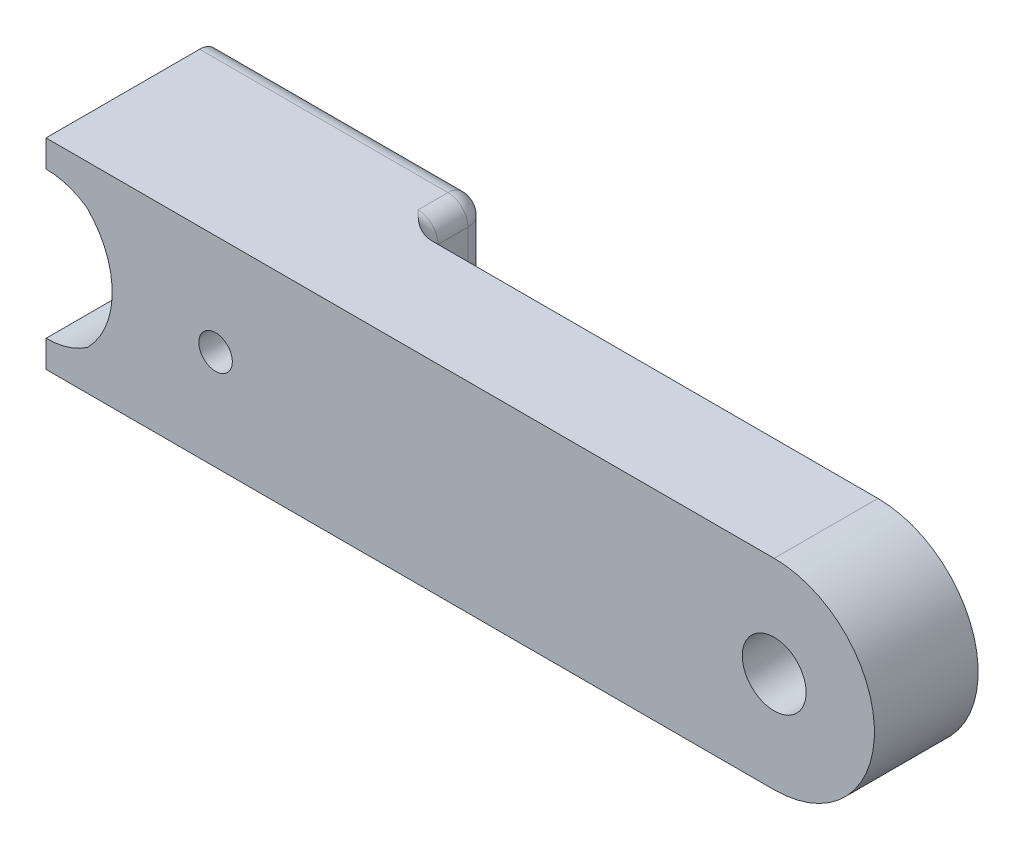
SolidWorks part; units mm, degrees
ref_plane "前视基准面" through (0, 0, 0) normal (0, 0, 1) x (1, 0, 0)
ref_plane "上视基准面" through (0, 0, 0) normal (0, 1, 0) x (1, 0, 0)
ref_plane "右视基准面" through (0, 0, 0) normal (1, 0, 0) x (0, 0, -1)
sketch "草图1" plane through (0, 0, 0) normal (0, 0, 1) x (1, 0, 0)
  line L0 (1.5398, 12.851) -> (15.553, 14.251)
  line L1 (-16.647, 18.901) -> (15.553, 18.901) construction
  line L2 (-16.647, 18.901) -> (-16.647, 12.851) construction
  line L3 (-16.647, 12.851) -> (15.553, 12.851) construction
  line L4 (15.553, 18.901) -> (15.553, 12.851) construction
  line L5 (-16.647, 18.901) -> (15.553, 12.851) construction
  line L6 (-16.647, 12.851) -> (15.553, 18.901) construction
  line L7 (14.1183, 17.876) -> (16.9877, 17.876) construction
  line L8 (14.1183, 17.876) -> (14.1183, 13.876) construction
  line L9 (14.1183, 13.876) -> (16.9877, 13.876) construction
  line L10 (16.9877, 17.876) -> (16.9877, 13.876) construction
  line L11 (14.1183, 17.876) -> (16.9877, 13.876) construction
  line L12 (14.1183, 13.876) -> (16.9877, 17.876) construction
  line L13 (15.553, 17.876) -> (1.5005, 18.901)
  line L14 (-0.547, 19.551) -> (-0.547, 12.201) construction
  line L15 (-0.547, 19.551) -> (-0.547, 20.901)
  line L16 (-0.547, 20.901) -> (19.5128, 20.901)
  line L17 (19.5128, 20.901) -> (35.953, 20.901)
  line L18 (-0.547, 12.201) -> (-0.547, 10.851)
  line L19 (-0.547, 10.851) -> (35.953, 10.851)
  line L20 (35.953, 20.901) -> (35.953, 10.851)
  line L21 (-0.547, 15.876) -> (3.9081, 15.876) construction
  circle A0 centre (-0.547, 15.876) radius 3.675 construction
  arc A1 (15.553, 14.251) -> (15.553, 17.876) centre (15.3719, 16.0635) ccw
  arc A2 (1.5398, 12.851) -> (-0.547, 12.201) centre (-0.547, 15.876) cw
  arc A3 (1.5005, 18.901) -> (-0.547, 19.551) centre (-0.547, 16.001) ccw
  point P6 (15.553, 15.876)
  dimension "D1" = 7.35
  dimension "D2" = 16.1
  dimension "D3" = 6.05
  dimension "D4" = 4
  dimension "D5" = 2
  dimension "D6" = 2
  dimension "D7" = 36.5
  dimension "D8" = 10.05
extrude "凸台-拉伸1" add sketch "草图1" along normal blind 2.2
sketch "草图2" plane through (0, 0, 0) normal (0, 0, -1) x (-1, 0, 0)
  line L1 (-35.953, 20.901) -> (0.547, 20.901)
  line L2 (-35.953, 20.901) -> (-35.953, 10.851)
  line L3 (-35.953, 10.851) -> (0.547, 10.851)
  line L4 (0.547, 20.901) -> (0.547, 10.851)
extrude "凸台-拉伸2" add sketch "草图2" along normal blind 3.25
sketch "草图3" plane through (0, 0, 2.2) normal (0, 0, 1) x (1, 0, 0)
  line L1 (-0.547, 20.901) -> (35.953, 20.901)
  line L3 (-0.547, 20.901) -> (-0.547, 10.851)
  line L4 (-0.547, 10.851) -> (35.953, 10.851)
  line L5 (35.953, 20.901) -> (35.953, 10.851)
extrude "凸台-拉伸3" add sketch "草图3" along normal blind 3.25
sketch "草图4" plane through (0, 0, 0) normal (0, 0, 1) x (1, 0, 0)
  line L0 (1.5005, 18.901) -> (1.5398, 12.851) construction
  line L1 (-0.547, 20.901) -> (-0.547, 10.851) construction
  line L2 (-0.547, 19.551) -> (-2.2354, 16.6161)
  line L3 (-2.2354, 16.6161) -> (-1.1109, 12.3105)
  line L4 (-1.1109, 12.3105) -> (-0.547, 12.201)
  arc A0 (1.5398, 12.851) -> (-0.547, 12.201) centre (-0.547, 15.876) cw
  arc A1 (-0.547, 19.551) -> (1.5398, 12.851) centre (-0.547, 15.876) ccw construction
  arc A2 (1.5005, 18.901) -> (-0.547, 19.551) centre (-0.547, 16.001) ccw
  arc A3 (1.5005, 18.901) -> (-0.547, 19.551) centre (-0.547, 16.001) ccw construction
  arc A4 (1.5005, 18.901) -> (1.5398, 12.851) centre (-1.5048, 15.8564) cw
extrude "切除-拉伸1" cut sketch "草图4" against normal mid plane 60
sketch "草图6" plane through (0, 0, -3.25) normal (0, 0, -1) x (-1, 0, 0)
  line L0 (-49.453, 15.876) -> (-51.7312, 15.876) construction
  line L1 (-35.953, 10.851) -> (-35.953, 20.901) construction
  circle A1 centre (-35.953, 15.876) radius 5.025
extrude "凸台-拉伸4" add sketch "草图6" against normal up to surface (8.7 mm away) up to face at (9.2639, 15.877, 5.45)
sketch "草图8" plane through (0, 0, -3.25) normal (0, 0, -1) x (-1, 0, 0)
  line L0 (0.547, 19.551) -> (0.547, 20.901) construction
  circle A0 centre (-49.453, 15.876) radius 1.675
  circle A1 centre (-7.953, 15.8564) radius 0.84
  dimension "D1" = 3.35
  dimension "D2" = 1.68
  dimension "D3" = 8.5
extrude "切除-拉伸3" cut sketch "草图8" against normal blind 55
sketch "草图9" plane through (0, 0, -3.25) normal (0, 0, -1) x (-1, 0, 0)
  line L1 (-12.8994, 22.3056) -> (-66.3159, 22.3056)
  line L2 (-12.8994, 22.3056) -> (-12.8994, 7.7732)
  line L3 (-12.8994, 7.7732) -> (-66.3159, 7.7732)
  line L4 (-66.3159, 22.3056) -> (-66.3159, 7.7732)
extrude "切除-拉伸4" cut sketch "草图9" against normal blind 3.5
sketch "草图10" plane through (0, 0, 5.45) normal (0, 0, 1) x (1, 0, 0)
  circle A0 centre (35.953, 15.876) radius 1.6
extrude "切除-拉伸5" cut sketch "草图10" against normal blind 10
sketch "草图11" plane through (0, 0, -3.25) normal (0, 0, -1) x (-1, 0, 0)
  line L0 (-12.8994, 13.2949) -> (0.7829, 10.851)
  line L1 (-12.8994, 10.851) -> (-12.8994, 13.9859) construction
  line L2 (0.7829, 10.851) -> (0, 8.7308)
  line L3 (0, 8.7308) -> (-15.448, 9.4154)
  line L4 (-15.448, 9.4154) -> (-12.8994, 13.2949)
extrude "切除-拉伸6" cut sketch "草图11" against normal up to surface (3.5 mm away) up to face at (37.553, 15.876, 0.25)
fillet "圆角1" radius 1 5 edges at (12.8994, 20.901, -1.5) (12.8994, 13.2949, -1.5) (6.1762, 12.094, -3.25) (12.8994, 17.0979, -3.25) (6.1762, 20.901, -3.25)
fillet "圆角2" radius 1 4 edges at (12.6167, 13.4353, 0.25) (5.7641, 12.0204, 0.25) (12.6065, 20.6081, 0.25) (12.8994, 18.9853, 0.25)
fillet "圆角3" radius 1 2 edges at (2.7732, 15.8842, 2.2) (2.7732, 15.8842, 0)
